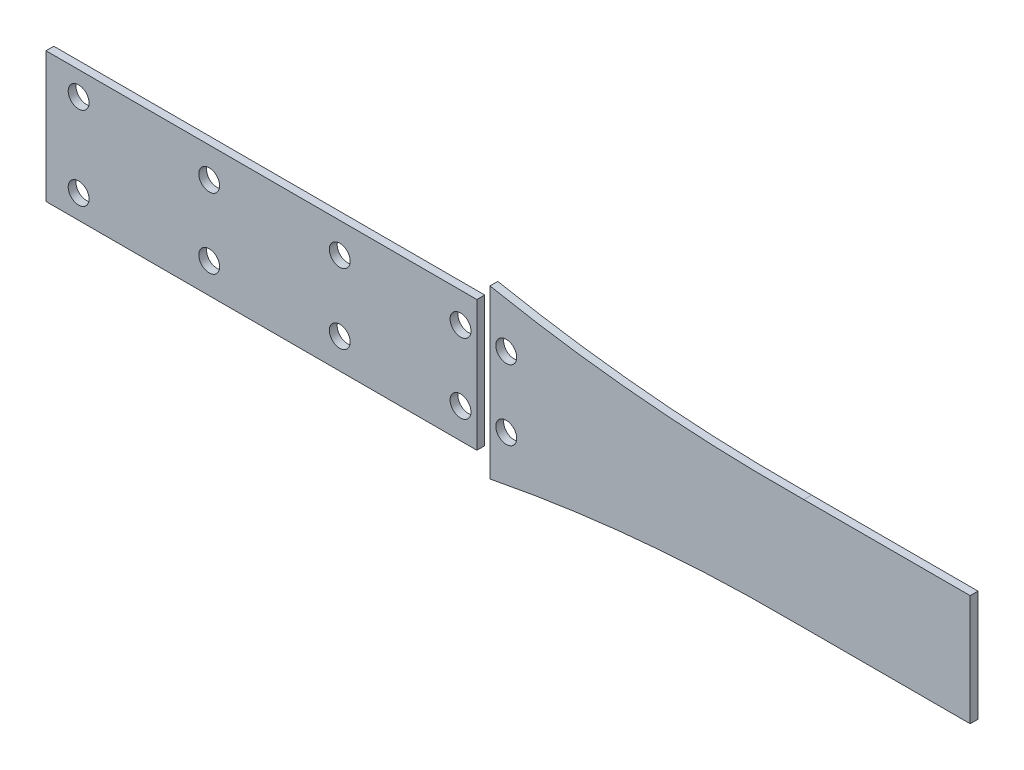
SolidWorks part; units mm, degrees
ref_plane "Front Plane" through (0, 0, 0) normal (0, 0, 1) x (1, 0, 0)
ref_plane "Top Plane" through (0, 0, 0) normal (0, 1, 0) x (1, 0, 0)
ref_plane "Right Plane" through (0, 0, 0) normal (1, 0, 0) x (0, 0, -1)
sketch "Sketch2" plane through (0, 0, 0) normal (0, 0, 1) x (1, 0, 0)
  line L0 (184.174, 14.5) -> (209.6614, 14.5)
  line L1 (209.6614, 14.5) -> (209.6614, -2.5)
  line L2 (209.6614, -2.5) -> (184.174, -2.5)
  line L3 (136.1014, -6.7946) -> (136.1014, 18.7946) construction
  line L4 (136.1014, -6.8054) -> (136.1014, 18.8054)
  spline S1 degree 3 poles (184.174, 14.5) (183.8243, 14.5) (182.9462, 14.5) (181.6678, 14.5) (180.8042, 14.5) (176.6959, 14.5) (170.0157, 14.6701) (160.6834, 15.2826) (151.3787, 16.2729) (144.7571, 17.2475) (139.4597, 18.166) (137.792, 18.4736) (136.1014, 18.8054) knots 0.04383 0.04383 0.04383 0.04383 0.045876 0.049176 0.052477 0.052477 0.082322 0.112168 0.142014 0.17186 0.17186 0.185263 0.185263 0.185263 0.185263
  spline S3 degree 3 poles (184.174, -2.5) (183.8243, -2.5) (182.9462, -2.5) (181.6678, -2.5) (180.8042, -2.5) (176.6959, -2.5) (170.0157, -2.6701) (160.6834, -3.2826) (151.3787, -4.2729) (144.7571, -5.2475) (139.4597, -6.166) (137.792, -6.4736) (136.1014, -6.8054) knots 0.04383 0.04383 0.04383 0.04383 0.045876 0.049176 0.052477 0.052477 0.082322 0.112168 0.142014 0.17186 0.17186 0.185263 0.185263 0.185263 0.185263
extrude "Boss-Extrude1" add sketch "Sketch2" along normal blind 0.6 and the other way blind 0.6 contours L4 S3 L2 L1 L0 S1 region at (170.5155, 6, 0)
sketch "Sketch3" plane through (0, 0, 0) normal (0, 0, 1) x (1, 0, 0)
  line L0 (196.3938, 6) -> (20, 6) construction
  line L1 (68.1014, -4) -> (134.1014, -4)
  line L2 (68.1014, -4) -> (68.1014, 16)
  line L3 (68.1014, 16) -> (134.1014, 16)
  line L4 (134.1014, -4) -> (134.1014, 16)
  line L5 (68.1014, -4) -> (134.1014, 16) construction
  line L6 (68.1014, 16) -> (134.1014, -4) construction
  line L7 (134.1014, -7.1964) -> (134.1014, 19.1964) construction
  line L8 (68.1014, 41.8477) -> (68.1014, 6) construction
  circle A0 centre (73.1014, 12.3713) radius 1.6 construction
  circle A1 centre (73.1014, -0.3713) radius 1.6 construction
  circle A2 centre (93.1014, 0.6287) radius 1.6 construction
  circle A3 centre (93.1014, 11.3713) radius 1.6 construction
  circle A4 centre (131.6014, 0.6287) radius 1.6 construction
  circle A5 centre (131.6014, 11.3713) radius 1.6 construction
  circle A6 centre (113.1014, 0.6287) radius 1.6 construction
  circle A7 centre (113.1014, 11.3713) radius 1.6 construction
  circle A8 centre (73.1014, 12.3713) radius 1.6
  circle A9 centre (73.1014, -0.3713) radius 1.6
  circle A10 centre (93.1014, 0.6287) radius 1.6
  circle A11 centre (93.1014, 11.3713) radius 1.6
  circle A12 centre (131.6014, 0.6287) radius 1.6
  circle A13 centre (131.6014, 11.3713) radius 1.6
  circle A14 centre (113.1014, 0.6287) radius 1.6
  circle A15 centre (113.1014, 11.3713) radius 1.6
  point P0 (101.1014, 6)
  dimension "D1" = 20
extrude "Boss-Extrude2" add sketch "Sketch3" along normal blind 0.6 and the other way blind 0.6 separate body
sketch "Sketch4" plane through (0, 0, 0) normal (0, 0, 1) x (1, 0, 0)
  circle A0 centre (138.6014, 11.3713) radius 1.6 construction
  circle A1 centre (138.6014, 11.3713) radius 1.6
  circle A2 centre (138.6014, 0.6287) radius 1.6 construction
  circle A3 centre (138.6014, 0.6287) radius 1.6
extrude "Cut-Extrude1" cut sketch "Sketch4" against normal through all both and the other way through all
